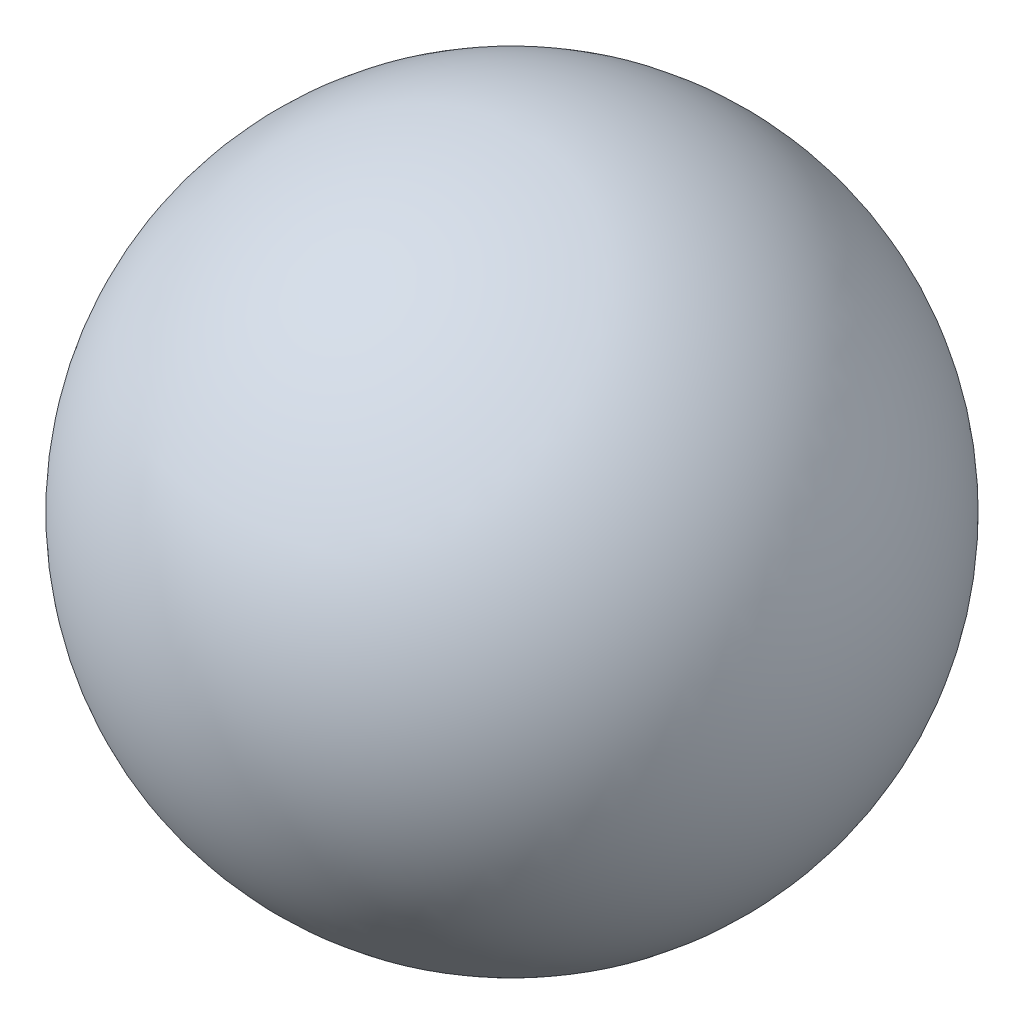
SolidWorks part; units mm, degrees
ref_plane "Front Plane" through (0, 0, 0) normal (0, 0, 1) x (1, 0, 0)
ref_plane "Top Plane" through (0, 0, 0) normal (0, 1, 0) x (1, 0, 0)
ref_plane "Right Plane" through (0, 0, 0) normal (1, 0, 0) x (0, 0, -1)
sketch "Sketch2" plane through (0, 0, 0) normal (1, 0, 0) x (0, 0, -1)
  line L0 (0, 247.65) -> (0, 0)
  arc A0 (0, 0) -> (0, 247.65) centre (0, 123.825) ccw
  point P4 (0, 123.825)
  dimension "D1" = 123.825
revolve "Revolve1" add sketch "Sketch2" angle 360 about L0
